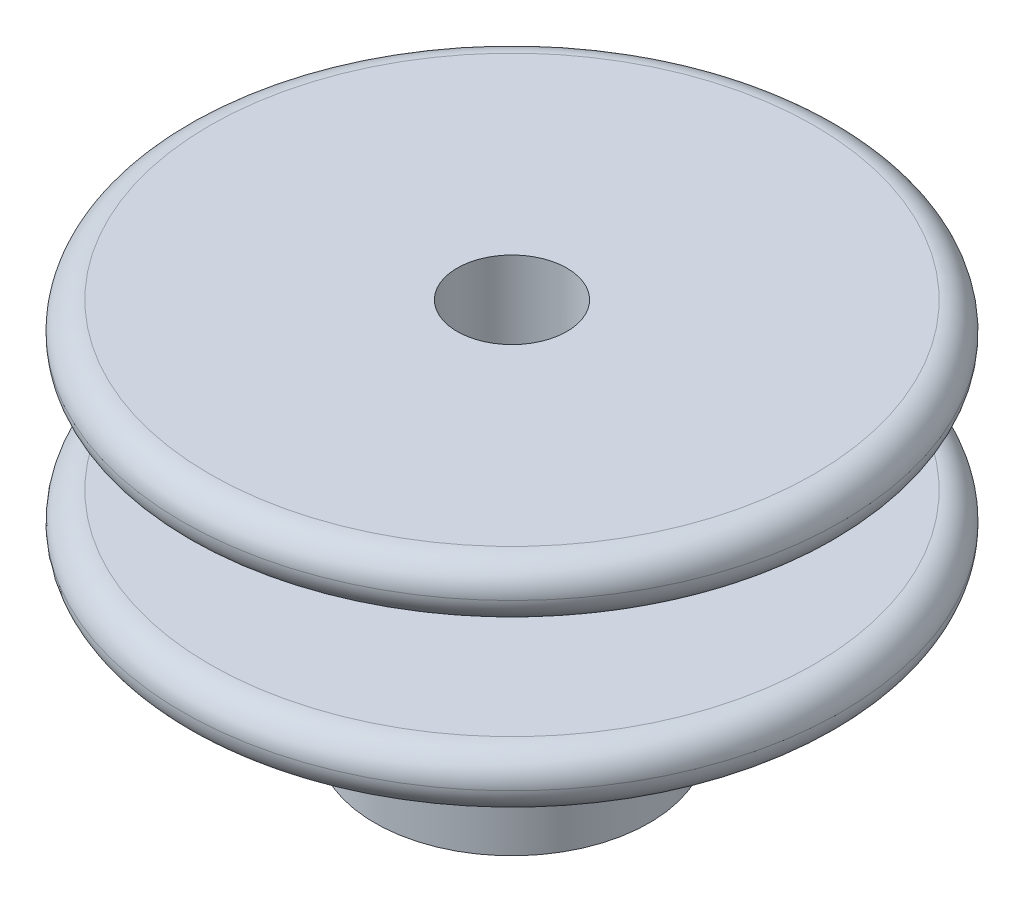
SolidWorks part; units mm, degrees
material "6061 合金"
ref_plane "前视基准面" through (0, 0, 0) normal (0, 0, 1) x (1, 0, 0)
ref_plane "上视基准面" through (0, 0, 0) normal (0, 1, 0) x (1, 0, 0)
ref_plane "右视基准面" through (0, 0, 0) normal (1, 0, 0) x (0, 0, -1)
other "Configuration Table"
sketch "草图1" plane through (0, 0, 0) normal (0, 1, 0) x (1, 0, 0)
  circle A0 centre (0, 0) radius 5
  dimension "D1" = 10
extrude "凸台-拉伸1" add sketch "草图1" along normal blind 4
sketch "草图2" plane through (0, 4, 0) normal (0, 1, 0) x (1, 0, 0)
  circle A0 centre (0, 0) radius 12
  dimension "D1" = 24
extrude "凸台-拉伸2" add sketch "草图2" along normal blind 2
sketch "草图3" plane through (0, 0, 0) normal (0, -1, 0) x (1, 0, 0)
  circle A0 centre (0, 0) radius 12
  dimension "D1" = 24
extrude "凸台-拉伸3" add sketch "草图3" along normal blind 2
sketch "草图4" plane through (0, -2, 0) normal (0, -1, 0) x (-1, 0, 0)
  circle A0 centre (0, 0) radius 5
extrude "凸台-拉伸4" add sketch "草图4" along normal blind 6
sketch "草图5" plane through (0, -8, 0) normal (0, -1, 0) x (1, 0, 0)
  circle A0 centre (0, 0) radius 2
extrude "切除-拉伸1" cut sketch "草图5" against normal through all
fillet "圆角2" radius 1 4 edges at (0, 0, -12) (0, 4, 12) (0, 6, 12) (0, -2, -12)
sketch "草图6" plane through (0, 0, 0) normal (0, 0, 1) x (1, 0, 0)
  line L1 (-5, -8) -> (5, -8) construction
  circle A0 centre (0, -4) radius 1
  dimension "D1" = 4
extrude "切除-拉伸2" cut sketch "草图6" against normal through all
cosmetic thread "装饰螺纹线1" parameters "D2"=3
